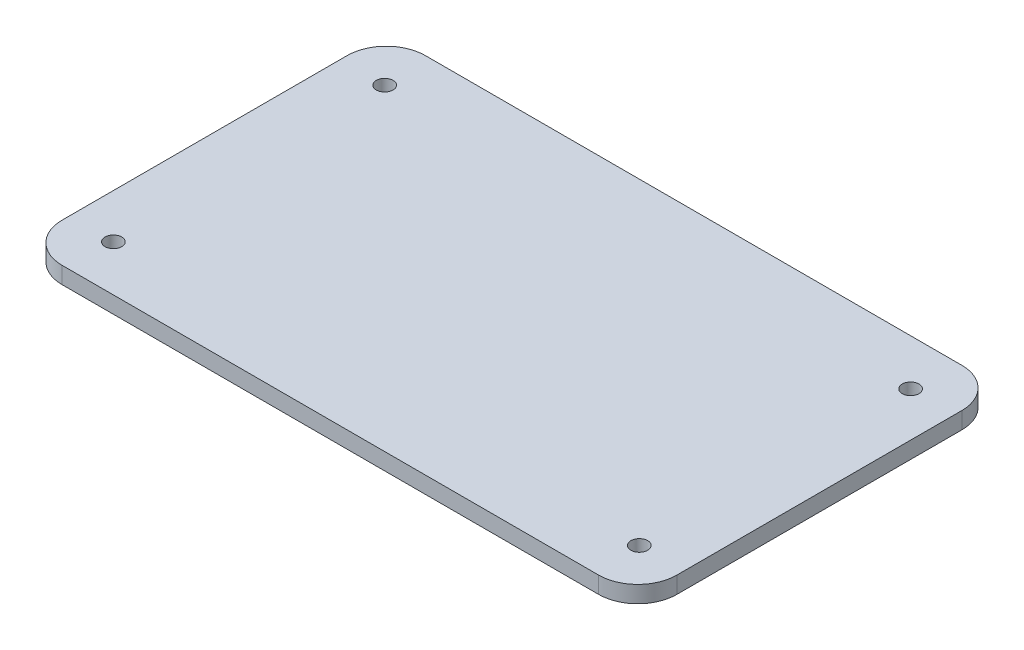
SolidWorks part; units mm, degrees
ref_plane "Front Plane" through (0, 0, 0) normal (0, 0, 1) x (1, 0, 0)
ref_plane "Top Plane" through (0, 0, 0) normal (0, 1, 0) x (1, 0, 0)
ref_plane "Right Plane" through (0, 0, 0) normal (1, 0, 0) x (0, 0, -1)
sketch "Sketch1" plane through (0, 0, 0) normal (0, 1, 0) x (1, 0, 0)
  line L1 (48, -32.5) -> (-48, -32.5)
  line L2 (55, -25.5) -> (55, 25.5)
  line L3 (48, 32.5) -> (-48, 32.5)
  line L4 (-55, -25.5) -> (-55, 25.5)
  line L5 (55, -32.5) -> (-55, 32.5) construction
  line L6 (55, 32.5) -> (-55, -32.5) construction
  line L7 (47.05, -24.27) -> (-47.05, -24.27) construction
  line L8 (47.05, -24.27) -> (47.05, 24.27) construction
  line L9 (47.05, 24.27) -> (-47.05, 24.27) construction
  line L10 (-47.05, -24.27) -> (-47.05, 24.27) construction
  line L11 (47.05, -24.27) -> (-47.05, 24.27) construction
  line L12 (47.05, 24.27) -> (-47.05, -24.27) construction
  circle A0 centre (-47.05, 24.27) radius 1.5
  circle A1 centre (-47.05, -24.27) radius 1.5
  circle A2 centre (47.05, -24.27) radius 1.5
  circle A3 centre (47.05, 24.27) radius 1.5
  arc A4 (-48, -32.5) -> (-55, -25.5) centre (-48, -25.5) cw
  arc A5 (48, -32.5) -> (55, -25.5) centre (48, -25.5) ccw
  arc A6 (55, 25.5) -> (48, 32.5) centre (48, 25.5) ccw
  arc A7 (-48, 32.5) -> (-55, 25.5) centre (-48, 25.5) ccw
  point P0 (0, 0)
  point P6 (0, 0)
  dimension "D5" = 7
  dimension "D1" = 110
  dimension "D2" = 65
  dimension "D3" = 94.1
  dimension "D4" = 48.54
extrude "Boss-Extrude1" add sketch "Sketch1" along normal mid plane 3
